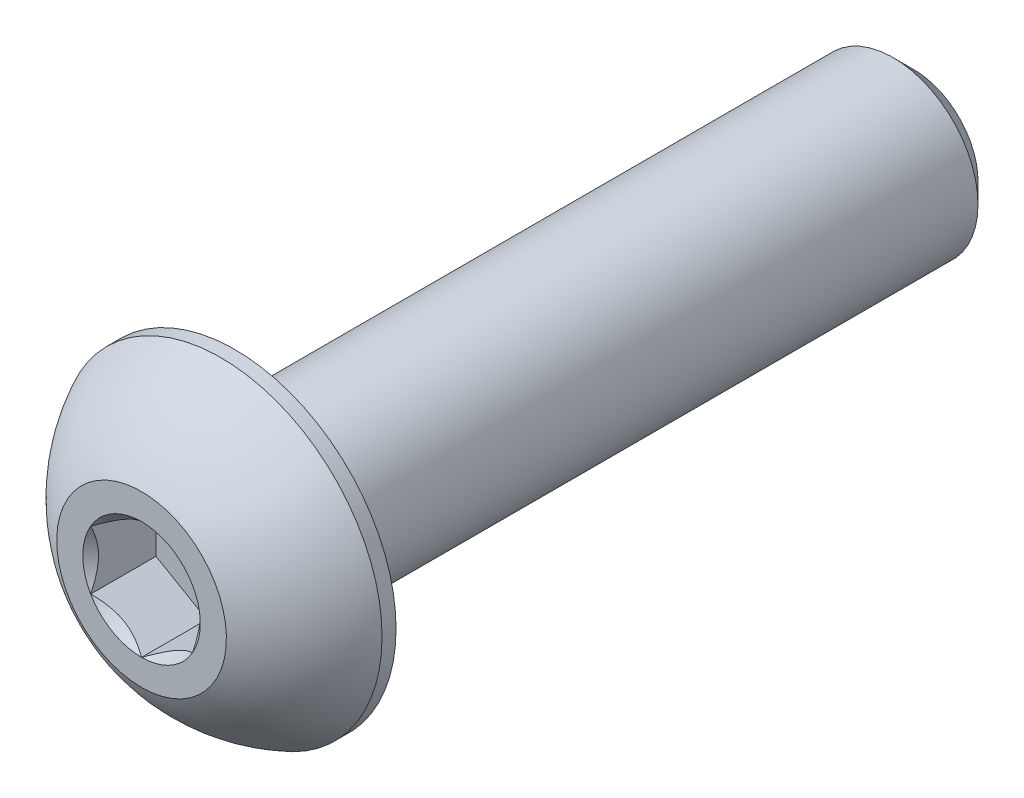
SolidWorks part; units mm, degrees
ref_plane "Front" through (0, 0, 0) normal (0, 0, 1) x (1, 0, 0)
ref_plane "Top" through (0, 0, 0) normal (0, 1, 0) x (1, 0, 0)
ref_plane "Right" through (0, 0, 0) normal (1, 0, 0) x (0, 0, -1)
sketch "Sketch1" plane through (0, 0, 0) normal (1, 0, 0) x (0, 0, -1)
  line L2 (2.75, 2.5) -> (22.75, 2.5)
  line L3 (22.75, 2.5) -> (22.75, 0)
  line L4 (22.75, 0) -> (2.75, 0)
  line L6 (2.3375, 4.75) -> (2.75, 4.75) construction
  line L7 (22.75, 2.5) -> (22.75, -2.5) construction
  line L8 (0, 0) -> (2.75, 0) construction
  line L9 (2.75, 4.75) -> (2.75, -4.75) construction
  line L11 (2.75, 2.5) -> (2.75, 0)
  line L13 (0, 1.5) -> (0, -1.5) construction
  line L14 (0, 1.5) -> (0, 2.5) construction
  line L15 (22.7, 2.5866) -> (23.1, 1.8938) construction
  line L16 (23.1, 1.8938) -> (23.5, 2.5866) construction
  line L17 (23.5, 2.5866) -> (22.7, 2.5866) construction
  line L18 (22.75, 2.5) -> (23.45, 2.5) construction
  line L19 (23.1, 2.5866) -> (23.1, 2.5) construction
  line L20 (23.1, 2.5) -> (23.1, 1.9804) construction
  line L21 (23.1, 1.9804) -> (23.1, 1.8938) construction
  line L22 (23.05, 1.9804) -> (23.15, 1.9804)
  line L23 (22.725, 2.5433) -> (23.475, 2.5433)
  line L24 (23.15, 1.9804) -> (23.475, 2.5433)
  line L25 (23.05, 1.9804) -> (22.725, 2.5433)
  line L26 (22.15, 2.5) -> (22.75, 1.9)
  arc A3 (0, 2.5) -> (2.3375, 4.75) centre (4.6581, 0) cw construction
  point P29 (23.1, 2.5433)
  point P30 (20.75, -2.5)
  dimension "D1" = 0.4125
  dimension "Pitch" = 0.8
  dimension "D3" = 0.1
  dimension "D2" = 0.6
  dimension "D4" = 45
  dimension "D5" = 2
sketch "Sketch10" plane through (0, 0, 0) normal (1, 0, 0) x (0, 0, -1)
  line L0 (22.15, 2.5) -> (22.75, 1.9) construction
  line L1 (22.15, 2.5) -> (22.75, 1.9)
  line L4 (22.75, 2.5) -> (2.75, 2.5)
  line L5 (22.75, 0) -> (22.75, 2.5)
  line L6 (2.75, 0) -> (22.75, 0)
  line L7 (2.75, 2.5) -> (2.75, 0)
  line L8 (22.15, 2.5) -> (2.75, 2.5)
  line L9 (22.75, 0) -> (22.75, 1.9)
  line L10 (2.75, 0) -> (22.75, 0)
  line L11 (2.75, 2.5) -> (2.75, 0)
  dimension "D1" = 0
revolve "Revolve3" add sketch "Sketch10" angle 360 about L8
sketch "Sketch7" plane through (0, 0, 0) normal (1, 0, 0) x (0, 0, -1)
  line L6 (2.3375, 4.75) -> (2.75, 4.75) construction
  line L8 (0, 0) -> (2.75, 0) construction
  line L11 (2.75, 4.75) -> (2.75, -4.75) construction
  line L12 (2.3375, 4.75) -> (2.75, 4.75)
  line L13 (0, 0) -> (2.75, 0)
  line L14 (0, 1.5) -> (0, -1.5) construction
  line L15 (2.75, 4.75) -> (2.75, 0)
  line L16 (0, 2.5) -> (0, 0)
  arc A2 (2.3375, 4.75) -> (0, 2.5) centre (4.6581, 0) ccw construction
  arc A3 (2.3375, 4.75) -> (0, 2.5) centre (4.6581, 0) ccw
revolve "Revolve2" add sketch "Sketch7" angle 360 mid plane about L13
sketch "Sketch5" plane through (0, 0, 0) normal (0, 0, 1) x (1, 0, 0)
  line L1 (1.5, -0.866) -> (1.5, 0.866)
  line L2 (1.5, 0.866) -> (0, 1.7321)
  line L3 (0, 1.7321) -> (-1.5, 0.866)
  line L4 (-1.5, 0.866) -> (-1.5, -0.866)
  line L5 (-1.5, -0.866) -> (0, -1.7321)
  line L6 (0, -1.7321) -> (1.5, -0.866)
  circle A0 centre (0, 0) radius 1.5 construction
extrude "Cut-Extrude2" cut sketch "Sketch5" against normal blind 1.925
sketch "Sketch6" plane through (0, 0, 0) normal (0, 0, 1) x (1, 0, 0)
  circle A0 centre (0, 0) radius 1.7321
extrude "Cut-Extrude3" cut sketch "Sketch6" against normal blind 1.925 draft 45
sketch "Sketch9" [suppressed] plane through (0, 0, -2.75) normal (0, 0, -1) x (-1, 0, 0)
  circle A0 centre (0, 0) radius 2.5 construction
  circle A4 centre (0, 0) radius 2.5
split "Split1" [suppressed] bodies to split 113
sketch "Sketch11" [suppressed] plane through (0, 0, -22.75) normal (0, 0, -1) x (-1, 0, 0)
  circle A0 centre (0, 0) radius 2.5 construction
  circle A1 centre (0, 0) radius 2.5
curve "Helix/Spiral1" [suppressed] pitch 0.8 height 22.75 turns 28.4375
sketch "Sketch12" [suppressed] plane through (0, 0, 0) normal (1, 0, 0) x (0, 0, -1)
  line L0 (23.05, 1.9804) -> (23.15, 1.9804) construction
  line L1 (23.15, 1.9804) -> (23.475, 2.5433) construction
  line L2 (22.725, 2.5433) -> (23.475, 2.5433) construction
  line L3 (23.05, 1.9804) -> (22.725, 2.5433) construction
  line L4 (23.05, 1.9804) -> (23.15, 1.9804)
  line L5 (23.15, 1.9804) -> (23.475, 2.5433)
  line L6 (22.725, 2.5433) -> (23.475, 2.5433)
  line L7 (23.05, 1.9804) -> (22.725, 2.5433)
sweep "Cut-Sweep2" [suppressed] cut profiles "Sketch12" path "Helix/Spiral1"
extrude "Boss-Extrude1" [suppressed] add sketch "Sketch9" along normal blind 10 draft 45
equation "\"D1@Cut-Extrude2\" = \"Head Ht@Sketch1\" * .7"
equation "\"D1@Sketch1\" = \"Head Ht@Sketch1\" * .15"
equation "\"D1@Cut-Extrude3\" = \"D1@Cut-Extrude2\""
equation "\"D3@Sketch1\" = \"Pitch@Sketch1\" / 8"
equation "\"D2@Sketch1\"=\"Pitch@Sketch1\"*0.75"
equation "\"D3@Helix/Spiral1\" = \"Lg@Sketch1\" + \"Head Ht@Sketch1\""
equation "\"D4@Helix/Spiral1\"=\"pitch@sketch1\""
equation "\"D5@Sketch1\"=\"Pitch@Sketch1\"*2.5"
